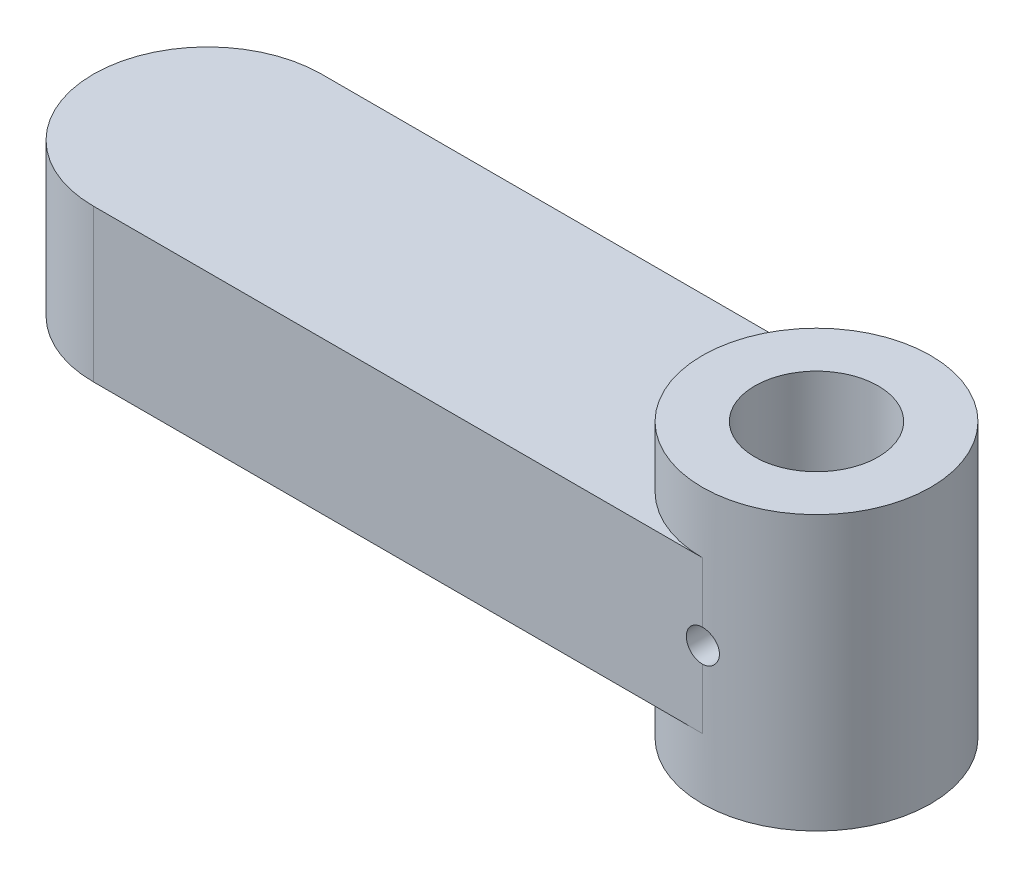
SolidWorks part; units mm, degrees
ref_plane "Front Plane" through (0, 0, 0) normal (0, 0, 1) x (1, 0, 0)
ref_plane "Top Plane" through (0, 0, 0) normal (0, 1, 0) x (1, 0, 0)
ref_plane "Right Plane" through (0, 0, 0) normal (1, 0, 0) x (0, 0, -1)
sketch "Sketch1" plane through (0, 0, 0) normal (0, 1, 0) x (1, 0, 0)
  line L0 (0, 7.5) -> (-40, 7.5)
  line L1 (-40, -7.5) -> (0, -7.5)
  circle A0 centre (0, 0) radius 4.05
  arc A1 (0, -7.5) -> (0, 7.5) centre (0, 0) ccw
  arc A2 (-40, 7.5) -> (-40, -7.5) centre (-40, 0) ccw
  dimension "D1" = 8.1
  dimension "D2" = 15
  dimension "D3" = 40
extrude "Boss-Extrude1" add sketch "Sketch1" along normal blind 10 contours L0 A2 L1 A1 A0 region at (-21.4212, 0, 0)
sketch "Sketch2" plane through (0, 0, -7.5) normal (0, 0, -1) x (-1, 0, 0)
  line L0 (0, 10) -> (0, 0) construction
  circle A0 centre (0, 5) radius 1.05
  dimension "D1" = 2.1
extrude "Cut-Extrude1" cut sketch "Sketch2" against normal through all
sketch "Sketch3" plane through (0, 0, -7.5) normal (0, 0, -1) x (-1, 0, 0)
  line L0 (41.4419, 7.2182) -> (0, 7.2182) construction
  line L2 (0, 10) -> (0, 6.05) construction
  line L3 (40.9291, 3.2182) -> (40.5701, 3.2182)
  line L4 (40.5701, 3.2182) -> (40.5701, 4.7415)
  line L5 (40.5701, 4.7415) -> (38.9026, 3.2182)
  line L6 (38.9026, 3.2182) -> (38.3906, 3.2182)
  line L7 (38.3906, 3.2182) -> (40.3562, 5.0131)
  line L8 (40.3562, 5.0131) -> (38.2368, 7.2182)
  line L9 (38.2368, 7.2182) -> (38.7151, 7.2182)
  line L10 (38.7151, 7.2182) -> (40.5701, 5.288)
  line L11 (40.5701, 5.288) -> (40.5701, 7.2182)
  line L12 (40.5701, 7.2182) -> (40.9291, 7.2182)
  line L13 (40.9291, 7.2182) -> (40.9291, 3.2182)
  line L14 (37.647, 3.2182) -> (36.8466, 3.2182)
  line L15 (36.5525, 5.3721) -> (35.0829, 7.2182)
  line L16 (35.0829, 7.2182) -> (35.5268, 7.2182)
  line L17 (35.5268, 7.2182) -> (36.9964, 5.3721)
  line L18 (36.9964, 5.3721) -> (37.2881, 5.3721)
  line L19 (37.2881, 5.3721) -> (37.2881, 7.2182)
  line L20 (37.2881, 7.2182) -> (37.647, 7.2182)
  line L21 (37.647, 7.2182) -> (37.647, 3.2182)
  line L22 (37.2881, 3.6285) -> (37.2881, 4.9618)
  line L23 (37.2881, 4.9618) -> (36.5557, 4.9674)
  line L24 (36.5381, 3.6285) -> (37.2881, 3.6285)
  line L25 (29.4419, 7.2182) -> (29.4419, 3.2182)
  line L26 (29.4419, 3.2182) -> (29.3666, 3.2182)
  line L27 (29.3666, 3.2182) -> (26.724, 6.3665)
  line L28 (26.724, 6.3665) -> (26.724, 3.2182)
  line L29 (26.724, 3.2182) -> (26.365, 3.2182)
  line L30 (26.365, 3.2182) -> (26.365, 7.2182)
  line L31 (26.365, 7.2182) -> (26.4467, 7.2182)
  line L32 (26.4467, 7.2182) -> (29.0829, 4.0772)
  line L33 (29.0829, 4.0772) -> (29.0829, 7.2182)
  line L34 (29.0829, 7.2182) -> (29.4419, 7.2182)
  line L35 (25.3393, 3.2182) -> (24.9804, 3.2182)
  line L36 (24.9804, 3.2182) -> (24.9804, 4.7415)
  line L37 (24.9804, 4.7415) -> (23.3129, 3.2182)
  line L38 (23.3129, 3.2182) -> (22.8009, 3.2182)
  line L39 (22.8009, 3.2182) -> (24.7664, 5.0131)
  line L40 (24.7664, 5.0131) -> (22.647, 7.2182)
  line L41 (22.647, 7.2182) -> (23.1254, 7.2182)
  line L42 (23.1254, 7.2182) -> (24.9804, 5.288)
  line L43 (24.9804, 5.288) -> (24.9804, 7.2182)
  line L44 (24.9804, 7.2182) -> (25.3393, 7.2182)
  line L45 (25.3393, 7.2182) -> (25.3393, 3.2182)
  line L46 (22.4675, 6.4466) -> (22.1294, 6.2439)
  line L47 (20.1599, 3.7928) -> (20.4844, 4.0388)
  line L48 (17.7496, 3.2182) -> (17.3906, 3.2182)
  line L49 (17.3906, 3.2182) -> (17.3906, 6.808)
  line L50 (17.3906, 6.808) -> (15.8522, 6.808)
  line L51 (15.8522, 6.808) -> (15.8522, 7.2182)
  line L52 (15.8522, 7.2182) -> (17.7496, 7.2182)
  line L53 (17.7496, 7.2182) -> (17.7496, 3.2182)
  line L54 (15.1855, 3.2182) -> (12.9291, 3.2182)
  line L55 (12.9291, 3.2182) -> (12.9291, 3.6285)
  line L56 (12.9291, 3.6285) -> (14.8265, 3.6285)
  line L57 (14.8265, 3.6285) -> (14.8265, 4.8593)
  line L58 (14.8265, 4.8593) -> (12.9291, 4.8593)
  line L59 (12.9291, 4.8593) -> (12.9291, 5.2695)
  line L60 (12.9291, 5.2695) -> (14.8265, 5.2695)
  line L61 (14.8265, 5.2695) -> (14.8265, 6.808)
  line L62 (14.8265, 6.808) -> (12.9291, 6.808)
  line L63 (12.9291, 6.808) -> (12.9291, 7.2182)
  line L64 (12.9291, 7.2182) -> (15.1855, 7.2182)
  line L65 (15.1855, 7.2182) -> (15.1855, 3.2182)
  line L66 (12.5188, 3.2182) -> (12.1342, 3.2182)
  line L67 (12.1342, 3.2182) -> (10.8009, 6.3705)
  line L68 (10.8009, 6.3705) -> (9.4675, 3.2182)
  line L69 (9.4675, 3.2182) -> (9.0829, 3.2182)
  line L70 (9.0829, 3.2182) -> (10.7752, 7.2182)
  line L71 (10.7752, 7.2182) -> (10.8265, 7.2182)
  line L72 (10.8265, 7.2182) -> (12.5188, 3.2182)
  line L73 (8.3137, 3.2182) -> (6.0573, 3.2182)
  line L74 (6.0573, 3.2182) -> (6.0573, 3.6285)
  line L75 (6.0573, 3.6285) -> (7.9547, 3.6285)
  line L76 (7.9547, 3.6285) -> (7.9547, 4.8593)
  line L77 (7.9547, 4.8593) -> (6.0573, 4.8593)
  line L78 (6.0573, 4.8593) -> (6.0573, 5.2695)
  line L79 (6.0573, 5.2695) -> (7.9547, 5.2695)
  line L80 (7.9547, 5.2695) -> (7.9547, 6.808)
  line L81 (7.9547, 6.808) -> (6.0573, 6.808)
  line L82 (6.0573, 6.808) -> (6.0573, 7.2182)
  line L83 (6.0573, 7.2182) -> (8.3137, 7.2182)
  line L84 (8.3137, 7.2182) -> (8.3137, 3.2182)
  line L85 (5.3393, 3.2182) -> (4.5389, 3.2182)
  line L86 (4.2448, 5.3721) -> (2.7752, 7.2182)
  line L87 (2.7752, 7.2182) -> (3.2192, 7.2182)
  line L88 (3.2192, 7.2182) -> (4.6887, 5.3721)
  line L89 (4.6887, 5.3721) -> (4.9804, 5.3721)
  line L90 (4.9804, 5.3721) -> (4.9804, 7.2182)
  line L91 (4.9804, 7.2182) -> (5.3393, 7.2182)
  line L92 (5.3393, 7.2182) -> (5.3393, 3.2182)
  line L93 (4.9804, 3.6285) -> (4.9804, 4.9618)
  line L94 (4.9804, 4.9618) -> (4.248, 4.9674)
  line L95 (4.2304, 3.6285) -> (4.9804, 3.6285)
  spline S0 degree 3 poles (36.8466, 3.2182) (36.744, 3.2188) (36.597, 3.2185) (36.4101, 3.2261) (36.2901, 3.2308) (36.1836, 3.2394) (36.068, 3.2494) (35.9884, 3.262) (35.9403, 3.2727) knots 0 0 0 0 0.338434 0.484822 0.617158 0.734698 0.837385 1 1 1 1
  spline S1 degree 3 poles (35.9403, 3.2727) (35.882, 3.2855) (35.7973, 3.3123) (35.6903, 3.3595) (35.615, 3.4008) (35.5439, 3.4479) (35.4771, 3.5009) (35.4153, 3.5602) (35.3564, 3.6235) (35.305, 3.6934) (35.2588, 3.7664) (35.2199, 3.8439) (35.1894, 3.9255) (35.1638, 4.0105) (35.1403, 4.1311) (35.1339, 4.2247) (35.1342, 4.288) knots 0 0 0 0 0.12704 0.188709 0.249085 0.309868 0.370231 0.430629 0.492277 0.554095 0.615218 0.676315 0.738476 0.800796 0.86521 1 1 1 1
  spline S2 degree 3 poles (35.1342, 4.288) (35.1339, 4.3918) (35.1515, 4.5458) (35.2198, 4.737) (35.2887, 4.8674) (35.3765, 4.9851) (35.4819, 5.0881) (35.6046, 5.1751) (35.7193, 5.2347) (35.8206, 5.2731) (35.9044, 5.3003) (35.9957, 5.3209) (36.0935, 5.3397) (36.1983, 5.3539) (36.3518, 5.368) (36.471, 5.3719) (36.5525, 5.3721) knots 0 0 0 0 0.153711 0.226699 0.299172 0.371166 0.442978 0.516334 0.592857 0.63351 0.676624 0.722915 0.771971 0.823829 0.879386 1 1 1 1
  spline S3 degree 3 poles (36.5557, 4.9674) (36.4894, 4.9685) (36.3935, 4.965) (36.2701, 4.9577) (36.1877, 4.9498) (36.1123, 4.9396) (36.0438, 4.9267) (35.9822, 4.9119) (35.9105, 4.8886) (35.8295, 4.8534) (35.7433, 4.7987) (35.668, 4.7326) (35.6053, 4.6561) (35.5551, 4.5716) (35.5078, 4.4499) (35.4926, 4.3526) (35.4932, 4.2872) knots 0 0 0 0 0.138878 0.201133 0.259059 0.312176 0.36059 0.404983 0.444989 0.518418 0.589383 0.657995 0.727586 0.795841 0.863197 1 1 1 1
  spline S4 degree 3 poles (35.4932, 4.2872) (35.4931, 4.2235) (35.5071, 4.1279) (35.5564, 4.0095) (35.6065, 3.9268) (35.669, 3.8522) (35.7417, 3.7886) (35.8231, 3.7358) (35.8984, 3.7009) (35.9663, 3.6804) (36.025, 3.6655) (36.0919, 3.6551) (36.1661, 3.6455) (36.2481, 3.6374) (36.3729, 3.6298) (36.4705, 3.6283) (36.5381, 3.6285) knots 0 0 0 0 0.136311 0.203719 0.273225 0.342608 0.411062 0.479239 0.549585 0.587914 0.630892 0.679007 0.732608 0.791193 0.85534 1 1 1 1
  spline S5 degree 3 poles (32.3906, 3.1157) (32.2452, 3.1161) (32.0297, 3.1329) (31.7529, 3.197) (31.5573, 3.2635) (31.3714, 3.3499) (31.1946, 3.4547) (31.0276, 3.579) (30.8707, 3.7198) (30.7281, 3.8747) (30.604, 4.0409) (30.4984, 4.2152) (30.4121, 4.3986) (30.3444, 4.5905) (30.2808, 4.8625) (30.2621, 5.0738) (30.2624, 5.2166) knots 0 0 0 0 0.130738 0.193341 0.25499 0.316108 0.377251 0.439385 0.502966 0.566515 0.628264 0.689118 0.749367 0.810186 0.871621 1 1 1 1
  spline S6 degree 3 poles (30.2624, 5.2166) (30.2622, 5.3584) (30.2808, 5.5685) (30.3446, 5.8387) (30.4113, 6.0302) (30.4976, 6.2133) (30.6034, 6.3877) (30.7272, 6.5544) (30.8692, 6.71) (31.0243, 6.8526) (31.1895, 6.9787) (31.3646, 7.0837) (31.5469, 7.1713) (31.7383, 7.2375) (32.0073, 7.3032) (32.2171, 7.3207) (32.3586, 7.3208) knots 0 0 0 0 0.128576 0.190331 0.251392 0.312186 0.373591 0.436092 0.500231 0.564355 0.626953 0.688358 0.749255 0.810088 0.871664 1 1 1 1
  spline S7 degree 3 poles (32.3586, 7.3208) (32.5014, 7.3211) (32.713, 7.3024) (32.9852, 7.2388) (33.1777, 7.1719) (33.3614, 7.0858) (33.5363, 6.9799) (33.7025, 6.8552) (33.8584, 6.7133) (34.0008, 6.5585) (34.1261, 6.3935) (34.2313, 6.2199) (34.3175, 6.0383) (34.3856, 5.8493) (34.4488, 5.5826) (34.468, 5.3756) (34.4675, 5.2359) knots 0 0 0 0 0.129755 0.192084 0.253475 0.314589 0.376095 0.438845 0.50309 0.56732 0.629682 0.690981 0.751436 0.811993 0.873142 1 1 1 1
  spline S8 degree 3 poles (34.4675, 5.2359) (34.4686, 5.1413) (34.4585, 5.0003) (34.4299, 4.8151) (34.3994, 4.6797) (34.36, 4.5469) (34.3115, 4.4171) (34.2559, 4.2891) (34.1897, 4.1655) (34.1175, 4.046) (34.0388, 3.9322) (33.953, 3.826) (33.8613, 3.7257) (33.7625, 3.6331) (33.6581, 3.5462) (33.5475, 3.4658) (33.4305, 3.3936) (33.3102, 3.3273) (33.1856, 3.2719) (33.0594, 3.223) (32.9305, 3.1841) (32.7991, 3.1532) (32.6195, 3.1248) (32.4826, 3.1146) (32.3906, 3.1157) knots 0 0 0 0 0.085881 0.128132 0.170168 0.211938 0.253861 0.29602 0.338574 0.38115 0.422821 0.464245 0.505121 0.54615 0.587164 0.628522 0.670271 0.71197 0.753242 0.794029 0.83487 0.875486 0.916539 1 1 1 1
  spline S9 degree 3 poles (32.373, 3.5259) (32.4486, 3.5249) (32.5613, 3.5335) (32.7097, 3.5567) (32.8189, 3.5817) (32.9265, 3.6138) (33.0327, 3.6534) (33.1375, 3.6996) (33.2399, 3.7533) (33.3384, 3.8134) (33.4335, 3.8768) (33.5217, 3.9471) (33.6045, 4.0217) (33.6818, 4.1015) (33.7536, 4.186) (33.8199, 4.2756) (33.8798, 4.3699) (33.9331, 4.4684) (33.9808, 4.5691) (34.0204, 4.6734) (34.0517, 4.7805) (34.0783, 4.8899) (34.1009, 5.0412) (34.1098, 5.1565) (34.1086, 5.2343) knots 0 0 0 0 0.083634 0.124968 0.166226 0.20759 0.249236 0.291612 0.334345 0.37721 0.419377 0.46086 0.501907 0.542696 0.583826 0.624645 0.666001 0.70743 0.748582 0.789398 0.830761 0.872086 0.914004 1 1 1 1
  spline S10 degree 3 poles (34.1086, 5.2343) (34.1089, 5.348) (34.0931, 5.5161) (34.0403, 5.7326) (33.9839, 5.8856) (33.912, 6.032) (33.8243, 6.1712) (33.7199, 6.3032) (33.6015, 6.4269) (33.4719, 6.5399) (33.3345, 6.6392) (33.1901, 6.7227) (33.0398, 6.7926) (32.8821, 6.8451) (32.6608, 6.8961) (32.489, 6.9115) (32.373, 6.9106) knots 0 0 0 0 0.126894 0.187739 0.24842 0.308586 0.36958 0.431822 0.496172 0.560657 0.623491 0.685245 0.746643 0.808335 0.870491 1 1 1 1
  spline S11 degree 3 poles (32.373, 6.9106) (32.2946, 6.9109) (32.1774, 6.9041) (32.0237, 6.8807) (31.9114, 6.8555) (31.8013, 6.8245) (31.6937, 6.7859) (31.5886, 6.7398) (31.4855, 6.6882) (31.3867, 6.6301) (31.2934, 6.5662) (31.2048, 6.4983) (31.1222, 6.4243) (31.0452, 6.3452) (30.9746, 6.2603) (30.9084, 6.1714) (30.8489, 6.0771) (30.7949, 5.9794) (30.7486, 5.8783) (30.709, 5.7745) (30.6771, 5.6679) (30.6521, 5.5587) (30.6287, 5.4082) (30.6204, 5.2933) (30.6214, 5.2158) knots 0 0 0 0 0.086551 0.129198 0.171463 0.21345 0.255405 0.297515 0.340093 0.382506 0.423874 0.46485 0.505557 0.546205 0.586587 0.627265 0.668477 0.709503 0.750389 0.791063 0.832001 0.873116 0.914597 1 1 1 1
  spline S12 degree 3 poles (30.6214, 5.2158) (30.6204, 5.1389) (30.6287, 5.0248) (30.6521, 4.8754) (30.6769, 4.7672) (30.709, 4.6619) (30.7485, 4.5597) (30.7951, 4.4601) (30.8486, 4.3635) (30.9088, 4.2707) (30.9745, 4.182) (31.0469, 4.0991) (31.124, 4.0198) (31.2075, 3.9459) (31.2976, 3.8776) (31.392, 3.8118) (31.4928, 3.7535) (31.5965, 3.6995) (31.7029, 3.6534) (31.8109, 3.6136) (31.9205, 3.5818) (32.0315, 3.5567) (32.182, 3.5335) (32.2963, 3.5249) (32.373, 3.5259) knots 0 0 0 0 0.085123 0.126464 0.16744 0.20796 0.24823 0.288728 0.329644 0.370509 0.411097 0.451784 0.492368 0.533445 0.575218 0.617559 0.660787 0.704052 0.746976 0.789185 0.831406 0.873248 0.915172 1 1 1 1
  spline S13 degree 3 poles (22.1294, 6.2439) (22.0709, 6.3455) (21.9784, 6.4881) (21.833, 6.6495) (21.7245, 6.7443) (21.6122, 6.8187) (21.4579, 6.889) (21.3335, 6.9108) (21.2512, 6.9106) knots 0 0 0 0 0.304646 0.438547 0.562322 0.677433 0.786897 1 1 1 1
  spline S14 degree 3 poles (21.2512, 6.9106) (21.1817, 6.9108) (21.0777, 6.8996) (20.945, 6.8593) (20.8504, 6.8189) (20.7627, 6.769) (20.6845, 6.7102) (20.6185, 6.6424) (20.5639, 6.5678) (20.5212, 6.4881) (20.4805, 6.3778) (20.4675, 6.2907) (20.4675, 6.2327) knots 0 0 0 0 0.18101 0.270405 0.360513 0.448738 0.532675 0.614376 0.694559 0.772714 0.849123 1 1 1 1
  spline S15 degree 3 poles (20.4675, 6.2327) (20.4669, 6.165) (20.4952, 6.0241) (20.5668, 5.8997) (20.611, 5.84) knots 0 0 0 0 0.475391 1 1 1 1
  spline S16 degree 3 poles (20.611, 5.84) (20.6474, 5.7908) (20.7114, 5.7185) (20.8066, 5.6232) (20.8921, 5.5457) (20.9873, 5.4639) (21.1337, 5.347) (21.2503, 5.26) (21.3321, 5.2022) knots 0 0 0 0 0.190099 0.299187 0.418362 0.548359 0.688775 1 1 1 1
  spline S17 degree 3 poles (21.3321, 5.2022) (21.413, 5.1455) (21.5265, 5.0617) (21.6678, 4.9518) (21.7568, 4.8815) (21.832, 4.816) (21.9109, 4.7457) (21.96, 4.6922) (21.9876, 4.6581) knots 0 0 0 0 0.347075 0.495559 0.629077 0.745524 0.845834 1 1 1 1
  spline S18 degree 3 poles (21.9876, 4.6581) (22.0229, 4.6123) (22.0723, 4.5421) (22.1247, 4.442) (22.1559, 4.3663) (22.1811, 4.2892) (22.2046, 4.1839) (22.2114, 4.1031) (22.2111, 4.0492) knots 0 0 0 0 0.26255 0.388252 0.511531 0.633734 0.755402 1 1 1 1
  spline S19 degree 3 poles (22.2111, 4.0492) (22.2114, 3.9654) (22.1954, 3.8411) (22.1425, 3.6837) (22.0861, 3.5744) (22.0162, 3.473) (21.9333, 3.3814) (21.8358, 3.3026) (21.7272, 3.2357) (21.6098, 3.1823) (21.4439, 3.1297) (21.313, 3.1166) (21.2256, 3.1157) knots 0 0 0 0 0.16577 0.246266 0.327682 0.408711 0.489625 0.571615 0.656207 0.741698 0.826557 1 1 1 1
  spline S20 degree 3 poles (21.2256, 3.1157) (21.132, 3.1149) (20.9921, 3.1338) (20.8141, 3.194) (20.7073, 3.2472) (20.6237, 3.2999) (20.56, 3.3479) (20.4951, 3.4032) (20.4297, 3.4667) (20.3631, 3.5373) (20.2705, 3.6447) (20.2034, 3.7314) (20.1599, 3.7928) knots 0 0 0 0 0.212613 0.318547 0.426489 0.48333 0.543275 0.607966 0.677192 0.750736 0.828748 1 1 1 1
  spline S21 degree 3 poles (20.4844, 4.0388) (20.5215, 3.9897) (20.578, 3.921) (20.653, 3.8346) (20.7065, 3.7806) (20.7555, 3.731) (20.804, 3.6892) (20.8499, 3.6541) (20.9077, 3.6165) (20.9811, 3.5801) (21.1036, 3.5379) (21.2009, 3.5261) (21.2656, 3.5259) knots 0 0 0 0 0.189596 0.274136 0.352122 0.4237 0.48904 0.548952 0.60191 0.70128 0.800434 1 1 1 1
  spline S22 degree 3 poles (21.2656, 3.5259) (21.3453, 3.5245) (21.4616, 3.5424) (21.6017, 3.6042) (21.6894, 3.6687) (21.7616, 3.7456) (21.8329, 3.8631) (21.852, 3.9651) (21.8522, 4.0323) knots 0 0 0 0 0.275822 0.401869 0.527875 0.650459 0.765964 1 1 1 1
  spline S23 degree 3 poles (21.8522, 4.0323) (21.853, 4.0755) (21.8447, 4.1399) (21.8209, 4.2234) (21.7958, 4.2858) (21.7615, 4.3497) (21.6957, 4.4415) (21.6337, 4.5059) (21.5885, 4.5492) knots 0 0 0 0 0.21612 0.323407 0.434613 0.553299 0.685993 1 1 1 1
  spline S24 degree 3 poles (21.5885, 4.5492) (21.568, 4.568) (21.5304, 4.599) (21.4707, 4.6434) (21.4096, 4.6898) (21.3365, 4.7436) (21.2154, 4.8298) (21.1193, 4.8993) (21.0509, 4.9474) knots 0 0 0 0 0.124952 0.218094 0.333502 0.468789 0.624938 1 1 1 1
  spline S25 degree 3 poles (21.0509, 4.9474) (20.9667, 5.0084) (20.8451, 5.0978) (20.6954, 5.222) (20.5977, 5.3092) (20.5098, 5.3933) (20.4327, 5.475) (20.366, 5.554) (20.2931, 5.6544) (20.2197, 5.779) (20.1366, 5.9786) (20.1086, 6.1353) (20.1086, 6.2383) knots 0 0 0 0 0.187763 0.272381 0.351302 0.424312 0.491882 0.554203 0.610843 0.715918 0.81455 1 1 1 1
  spline S26 degree 3 poles (20.1086, 6.2383) (20.1075, 6.3094) (20.119, 6.4146) (20.1531, 6.5507) (20.1904, 6.6477) (20.2372, 6.7414) (20.2942, 6.8317) (20.3632, 6.9172) (20.4399, 6.9995) (20.5251, 7.0738) (20.6153, 7.1401) (20.7098, 7.1968) (20.81, 7.2414) (20.914, 7.277) (21.0604, 7.3117) (21.1744, 7.3211) (21.2512, 7.3208) knots 0 0 0 0 0.121779 0.180926 0.240265 0.299715 0.360503 0.423144 0.488 0.553287 0.616917 0.679809 0.742178 0.804656 0.868254 1 1 1 1
  spline S27 degree 3 poles (21.2512, 7.3208) (21.3113, 7.3211) (21.4002, 7.3141) (21.517, 7.294) (21.6012, 7.2714) (21.6837, 7.2432) (21.7639, 7.2088) (21.8418, 7.1678) (21.9177, 7.1201) (21.9921, 7.0652) (22.0647, 7.0018) (22.1361, 6.9301) (22.2063, 6.8505) (22.2739, 6.7613) (22.3651, 6.6284) (22.4273, 6.5211) (22.4675, 6.4466) knots 0 0 0 0 0.1137 0.168686 0.224158 0.278721 0.333797 0.389247 0.4454 0.503285 0.564258 0.627941 0.694626 0.765364 0.839605 1 1 1 1
  spline S28 degree 3 poles (4.5389, 3.2182) (4.4363, 3.2188) (4.2893, 3.2185) (4.1024, 3.2261) (3.9824, 3.2308) (3.8759, 3.2394) (3.7603, 3.2494) (3.6807, 3.262) (3.6326, 3.2727) knots 0 0 0 0 0.338434 0.484822 0.617158 0.734698 0.837385 1 1 1 1
  spline S29 degree 3 poles (3.6326, 3.2727) (3.5743, 3.2855) (3.4896, 3.3123) (3.3826, 3.3595) (3.3073, 3.4008) (3.2362, 3.4479) (3.1694, 3.5009) (3.1076, 3.5602) (3.0487, 3.6235) (2.9974, 3.6934) (2.9511, 3.7664) (2.9122, 3.8439) (2.8817, 3.9255) (2.8561, 4.0105) (2.8326, 4.1311) (2.8262, 4.2247) (2.8265, 4.288) knots 0 0 0 0 0.12704 0.188709 0.249085 0.309868 0.370231 0.430629 0.492277 0.554095 0.615218 0.676315 0.738476 0.800796 0.86521 1 1 1 1
  spline S30 degree 3 poles (2.8265, 4.288) (2.8262, 4.3918) (2.8438, 4.5458) (2.9121, 4.737) (2.981, 4.8674) (3.0688, 4.9851) (3.1742, 5.0881) (3.2969, 5.1751) (3.4116, 5.2347) (3.513, 5.2731) (3.5967, 5.3003) (3.688, 5.3209) (3.7858, 5.3397) (3.8906, 5.3539) (4.0442, 5.368) (4.1633, 5.3719) (4.2448, 5.3721) knots 0 0 0 0 0.153711 0.226699 0.299172 0.371166 0.442978 0.516334 0.592857 0.63351 0.676624 0.722915 0.771971 0.823829 0.879386 1 1 1 1
  spline S31 degree 3 poles (4.248, 4.9674) (4.1817, 4.9685) (4.0858, 4.965) (3.9624, 4.9577) (3.88, 4.9498) (3.8046, 4.9396) (3.7361, 4.9267) (3.6745, 4.9119) (3.6028, 4.8886) (3.5218, 4.8534) (3.4357, 4.7987) (3.3603, 4.7326) (3.2976, 4.6561) (3.2474, 4.5716) (3.2001, 4.4499) (3.1849, 4.3526) (3.1855, 4.2872) knots 0 0 0 0 0.138878 0.201133 0.259059 0.312176 0.36059 0.404983 0.444989 0.518418 0.589383 0.657995 0.727586 0.795841 0.863197 1 1 1 1
  spline S32 degree 3 poles (3.1855, 4.2872) (3.1855, 4.2235) (3.1994, 4.1279) (3.2487, 4.0095) (3.2988, 3.9268) (3.3613, 3.8522) (3.434, 3.7886) (3.5154, 3.7358) (3.5908, 3.7009) (3.6586, 3.6804) (3.7173, 3.6655) (3.7842, 3.6551) (3.8584, 3.6455) (3.9405, 3.6374) (4.0652, 3.6298) (4.1628, 3.6283) (4.2304, 3.6285) knots 0 0 0 0 0.136311 0.203719 0.273225 0.342608 0.411062 0.479239 0.549585 0.587914 0.630892 0.679007 0.732608 0.791193 0.85534 1 1 1 1
extrude "Cut-Extrude2" cut sketch "Sketch3" against normal blind 2
sketch "Sketch4" plane through (0, 0, 0) normal (0, -1, 0) x (1, 0, 0)
  circle A0 centre (0, 0) radius 7.5
  circle A1 centre (0, 0) radius 4.05
  circle A2 centre (0, 0) radius 4.05 construction
  circle M3 centre (0, 0) radius 4.05
  arc M5 (0, -7.5) -> (0, 7.5) centre (0, 0) ccw
  dimension "D1" = 15
extrude "Boss-Extrude2" add sketch "Sketch4" along normal blind 4 contours A0 M5 M3 region at (5.1533, 0, -5.1533)
extrude "Boss-Extrude3" add sketch "Sketch4<4>" against normal blind 4 from surface starting at face at (0, 10, 4.05)
sketch "Sketch4<4>" plane through (0, 0, 0) normal (0, -1, 0) x (1, 0, 0) same geometry as "Sketch4"
